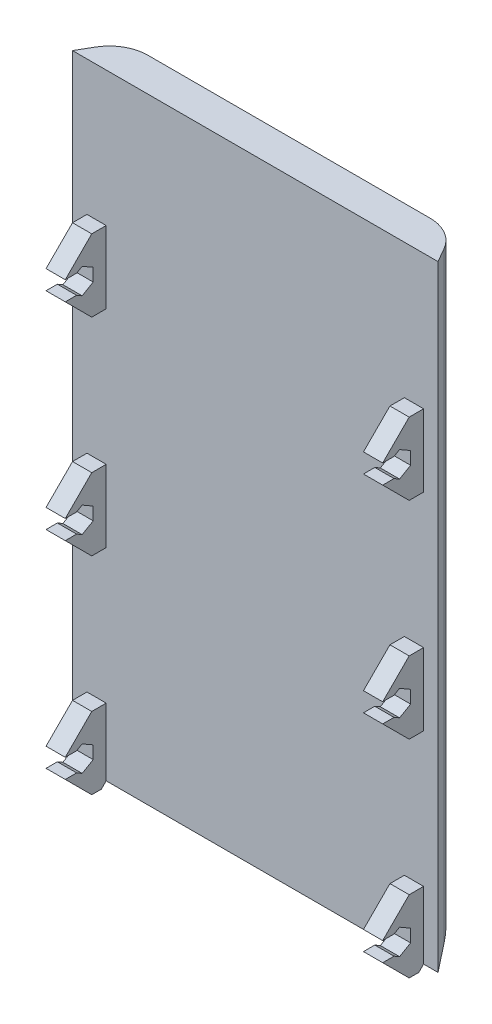
SolidWorks part; units mm, degrees
ref_plane "Front Plane" through (0, 0, 0) normal (0, 0, 1) x (1, 0, 0)
ref_plane "Top Plane" through (0, 0, 0) normal (0, 1, 0) x (1, 0, 0)
ref_plane "Right Plane" through (0, 0, 0) normal (1, 0, 0) x (0, 0, -1)
sketch "Sketch1" plane through (0, 0, 0) normal (0, 1, 0) x (1, 0, 0)
  line L0 (-9.2151, 0) -> (-9.2151, -10)
  line L1 (-9.2151, -10) -> (-5.2151, -10)
  line L2 (-5.2151, -10) -> (-5.2151, 0)
  line L3 (-5.2151, 0) -> (56.7849, 0)
  line L4 (56.7849, 0) -> (56.7849, -10)
  line L5 (56.7849, -10) -> (60.7849, -10)
  line L6 (60.7849, -10) -> (60.7849, 0)
  line L7 (60.7849, 0) -> (63.7849, 0)
  line L8 (-9.2151, 0) -> (-12.2151, 0)
  line L9 (-12.2151, 0) -> (-8.1737, 7)
  line L10 (-8.1737, 7) -> (59.7434, 7)
  line L11 (59.7434, 7) -> (63.7849, 0)
  line L12 (25.7849, 7) -> (25.7849, 0) construction
  dimension "D1" = 3
  dimension "D2" = 10
  dimension "D3" = 70
  dimension "D4" = 7
  dimension "D5" = 4
  dimension "D6" = 60
extrude "Boss-Extrude1" add sketch "Sketch1" along normal blind 129
sketch "Sketch4" plane through (60.7849, 0, 0) normal (1, 0, 0) x (0, 0, -1)
  line L0 (0, 129) -> (0, 0) construction
  line L1 (-37.5185, 129) -> (0, 129)
  line L2 (-37.5185, 129) -> (-37.5185, 101)
  line L3 (-37.5185, 101) -> (0, 101)
  line L4 (0, 129) -> (0, 101)
  line L5 (-37.5185, 129) -> (0, 101) construction
  line L6 (-37.5185, 101) -> (0, 129) construction
  line L7 (-10, 129) -> (0, 129) construction
  point P0 (-18.7592, 115)
  dimension "D1" = 28
extrude "Cut-Extrude1" cut sketch "Sketch4" against normal through all
sketch "Sketch5" plane through (60.7849, 0, 0) normal (1, 0, 0) x (0, 0, -1)
  line L0 (0, 129) -> (0, 0) construction
  line L1 (-33.3149, 86) -> (0, 86)
  line L2 (-33.3149, 86) -> (-33.3149, 58)
  line L3 (-33.3149, 58) -> (0, 58)
  line L4 (0, 86) -> (0, 58)
  line L5 (-33.3149, 86) -> (0, 58) construction
  line L6 (-33.3149, 58) -> (0, 86) construction
  line L7 (-10, 101) -> (0, 101) construction
  point P0 (-16.6574, 72)
  dimension "D1" = 28
  dimension "D2" = 15
extrude "Cut-Extrude2" cut sketch "Sketch5" against normal through all
sketch "Sketch6" plane through (0, 0, 0) normal (1, 0, 0) x (0, 0, -1)
  line L0 (-10, 101) -> (-10, 86) construction
  line L1 (-2.7, 94.8279) -> (-5, 96.1558)
  line L2 (-5, 96.1558) -> (-7.3, 94.8279)
  line L3 (-7.3, 94.8279) -> (-7.3, 92.1721)
  line L4 (-7.3, 92.1721) -> (-5, 90.8442)
  line L5 (-5, 90.8442) -> (-2.7, 92.1721)
  line L6 (-2.7, 92.1721) -> (-2.7, 94.8279)
  line L7 (-10, 101) -> (0, 101) construction
  line L8 (-6.15, 95.4919) -> (-10, 95.4919)
  line L9 (-6.15, 91.5081) -> (-10, 91.5081)
  line L10 (-10, 91.5081) -> (-10, 95.4919)
  circle A1 centre (-5, 93.5) radius 2.3 construction
  dimension "D1" = 4.6
  dimension "D2" = 7.5
  dimension "D3" = 5
extrude "Cut-Extrude3" cut sketch "Sketch6" against normal through all and the other way through all contours L10 L9 L4 L3 L2 L8 | L5 L6 L1 L2 L3 L4 region at (0, 93.5, 5) region at (0, 93.5, 8.5351)
pattern_linear "LPattern1" count 4 spacing 43 along (0, -1, 0) of "Cut-Extrude2", "Cut-Extrude3"
chamfer "Chamfer6" distance 8 angle 45 1 edges at (25.7849, 0, -7)
fillet "Fillet1" radius 8 2 edges at (-8.1737, 68.5, -7) (59.7434, 68.5, -7)
chamfer "Chamfer5" distance 7 angle 45 12 edges at (58.7849, 101, 10) (58.7849, 86, 10) (-7.2151, 101, 10) (-7.2151, 86, 10) (-7.2151, 58, 10) (-7.2151, 43, 10) (58.7849, 58, 10) (58.7849, 43, 10) (58.7849, 15, 10) (58.7849, 0, 10) (-7.2151, 0, 10) (-7.2151, 15, 10)
sketch "Sketch7" plane through (0, 0, -7) normal (0, 0, -1) x (-1, 0, 0)
  line L0 (-40.1246, 129) -> (-40.1246, 21.6303) construction
  line L1 (-55.1246, 129) -> (3.5549, 129) construction
  line L3 (-55.1246, 129) -> (-55.1246, 8) construction
  text T0 "ROAB LAB" font "VALORANT" height in points 48
  dimension "D1" = 15
extrude "Cut-Extrude4" cut sketch "Sketch7" against normal blind 1
